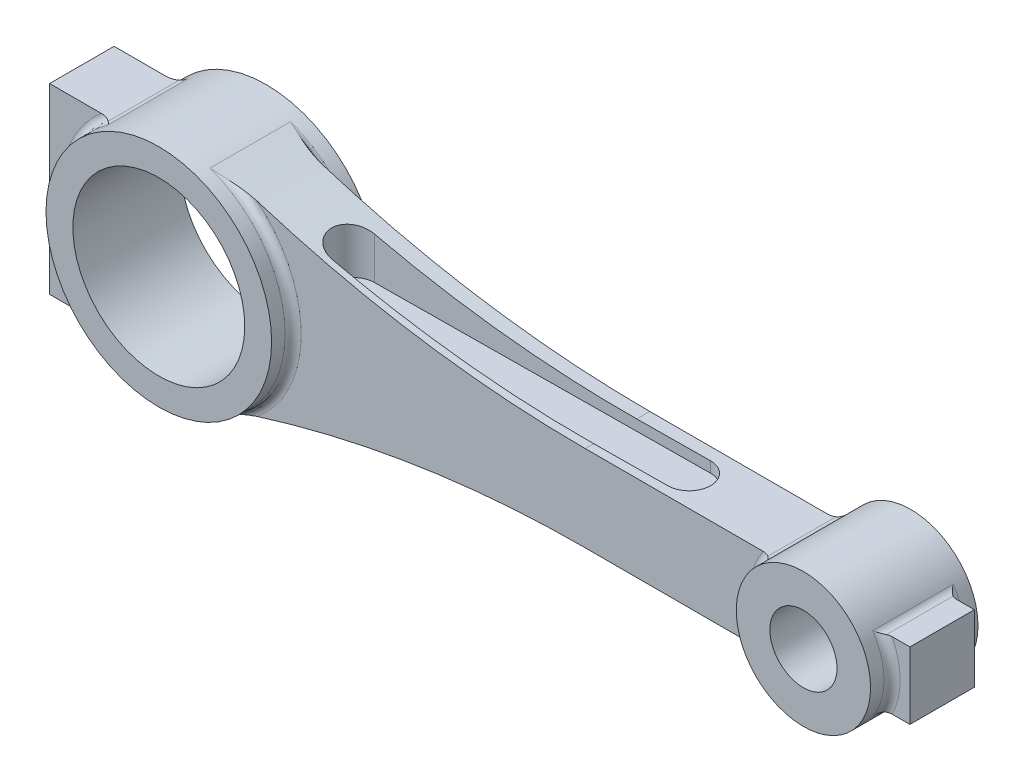
SolidWorks part; units mm, degrees
ref_plane "Front Plane" through (0, 0, 0) normal (0, 0, 1) x (1, 0, 0)
ref_plane "Top Plane" through (0, 0, 0) normal (0, 1, 0) x (1, 0, 0)
ref_plane "Right Plane" through (0, 0, 0) normal (1, 0, 0) x (0, 0, -1)
sketch "Sketch1" plane through (0, 0, 0) normal (0, 0, 1) x (1, 0, 0)
  circle A0 centre (-320.1813, 0) radius 160
  circle A1 centre (-320.1813, 0) radius 210
  circle A2 centre (879.8187, 0) radius 62.5
  circle A3 centre (879.8187, 0) radius 125
  dimension "D1" = 420
  dimension "D2" = 320
  dimension "D3" = 250
  dimension "D4" = 125
  dimension "D5" = 1200
extrude "Boss-Extrude2" add sketch "Sketch1" along normal mid plane 200
sketch "Sketch2" plane through (0, 0, 0) normal (0, 0, 1) x (1, 0, 0)
  line L0 (433.7719, 80) -> (783.7719, 80)
  line L1 (879.8187, 0) -> (-110.1813, 0) construction
  line L2 (433.7719, -80) -> (783.7719, -80)
  circle A0 centre (879.8187, 0) radius 125 construction
  circle A1 centre (-320.1813, 0) radius 210 construction
  arc A2 (783.7719, 80) -> (783.7719, -80) centre (879.8187, 0) ccw
  arc A3 (-249.8538, -197.8738) -> (-249.8538, 197.8738) centre (-320.1813, 0) ccw
  arc A4 (433.7719, 80) -> (-249.8538, 197.8738) centre (433.7719, 2121.3282) cw
  arc A5 (433.7719, -80) -> (-249.8538, -197.8738) centre (433.7719, -2121.3282) ccw
  dimension "D1" = 350
  dimension "D2" = 80
extrude "Boss-Extrude3" add sketch "Sketch2" along normal mid plane 120
sketch "Sketch3" plane through (0, 0, 0) normal (0, 0, 1) x (1, 0, 0)
  line L0 (-443.4696, 170) -> (-563.4696, 170)
  line L1 (-563.4696, 170) -> (-563.4696, -170)
  line L2 (-563.4696, -170) -> (-443.4696, -170)
  line L3 (1038.0719, 62.5) -> (988.0719, 62.5)
  line L4 (1038.0719, 62.5) -> (1038.0719, -62.5)
  line L5 (1038.0719, -62.5) -> (988.0719, -62.5)
  circle A0 centre (-320.1813, 0) radius 210 construction
  arc A1 (-443.4696, 170) -> (-443.4696, -170) centre (-320.1813, 0) ccw
  circle A2 centre (879.8187, 0) radius 125 construction
  arc A3 (988.0719, -62.5) -> (988.0719, 62.5) centre (879.8187, 0) ccw
  point P11 (0, 0)
  dimension "D1" = 340
  dimension "D2" = 120
  dimension "D3" = 50
  dimension "D4" = 125
extrude "Boss-Extrude4" add sketch "Sketch3" along normal mid plane 120
ref_plane "Plane1" through (0, 60, 0) normal (0, 1, 0) x (1, 0, 0)
sketch "Sketch4" plane through (0, 60, 0) normal (0, 1, 0) x (1, 0, 0)
  line L0 (-49.8538, -8.443) -> (570.1462, -2.9971) construction
  line L1 (-50.2052, 31.5554) -> (569.7948, 37.0014)
  line L2 (-49.5025, -48.4415) -> (570.4975, -42.9955)
  line L3 (-249.8538, -60) -> (-249.8538, 60) construction
  arc A0 (-50.2052, 31.5554) -> (-49.5025, -48.4415) centre (-49.8538, -8.443) ccw
  arc A1 (570.4975, -42.9955) -> (569.7948, 37.0014) centre (570.1462, -2.9971) ccw
  point P2 (260.1462, -5.72)
  dimension "D1" = 40
  dimension "D2" = 200
  dimension "D3" = 620
extrude "Cut-Extrude1" cut sketch "Sketch4" along normal blind 120
mirror "Mirror1" about plane through (0, 0, 0) normal (0, 1, 0) of "Cut-Extrude1"
fillet "Fillet1" radius 15 10 edges at (783.7719, 80, 0) (783.7719, -80, 0) (1004.8187, 0, 60) (988.0719, -62.5, 0) (1004.8187, 0, -60) (988.0719, 62.5, 0) (-443.4696, 170, 0) (-443.4696, -170, 0) (-530.1813, 0, -60) (-530.1813, 0, 60)
fillet "Fillet2" radius 15 4 edges at (-110.1813, 0, 60) (-110.1813, 0, -60) (754.8187, 0, -60) (754.8187, 0, 60)
